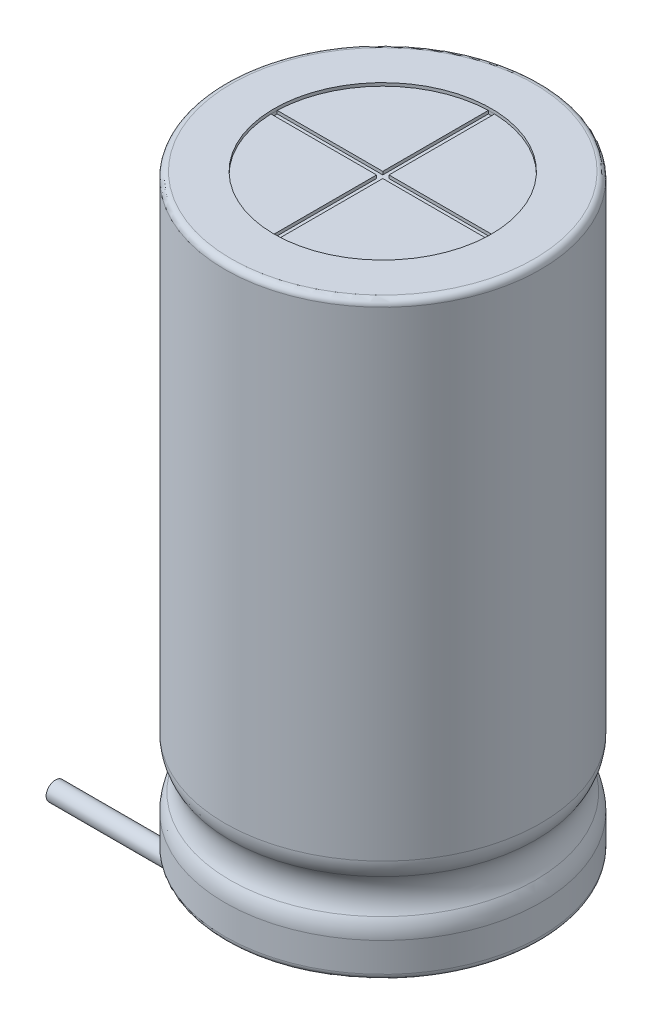
SolidWorks part; units mm, degrees
ref_plane "Płaszczyzna przednia" through (0, 0, 0) normal (0, 0, 1) x (1, 0, 0)
ref_plane "Płaszczyzna górna" through (0, 0, 0) normal (0, 1, 0) x (1, 0, 0)
ref_plane "Płaszczyzna prawa" through (0, 0, 0) normal (1, 0, 0) x (0, 0, -1)
sketch "Szkic1" plane through (0, 0, 0) normal (1, 0, 0) x (0, 0, -1)
  line L0 (0, 0) -> (4.88, 0)
  line L1 (5.08, 0.2) -> (5.08, 1.1437)
  line L2 (4.88, 19) -> (0, 19)
  line L3 (0, 19) -> (0, 0)
  line L4 (5.08, 3.3563) -> (5.08, 18.8)
  arc A0 (4.9162, 1.6927) -> (4.9162, 2.8073) centre (5.7673, 2.25) cw
  arc A1 (5.08, 18.8) -> (4.88, 19) centre (4.88, 18.8) ccw
  arc A2 (4.88, 0) -> (5.08, 0.2) centre (4.88, 0.2) ccw
  arc A3 (4.9162, 2.8073) -> (5.08, 3.3563) centre (4.0778, 3.3563) ccw
  arc A4 (4.9162, 1.6927) -> (5.08, 1.1437) centre (4.0778, 1.1437) cw
  point P8 (5.08, 19)
  point P11 (5.08, 0)
  point P17 (5.08, 3)
  dimension "D5" = 0.2
  dimension "D6" = 1.0022
  dimension "D3" = 1.0173
  dimension "D1" = 5.08
  dimension "D2" = 19
  dimension "D4" = 4.9162
  dimension "D7" = 1.1437
revolve "Obrót1" add sketch "Szkic1" angle 360 about L3
sketch "Szkic2" plane through (0, 19, 0) normal (0, 1, 0) x (1, 0, 0)
  circle A0 centre (0, 0) radius 3.5
  dimension "D1" = 7
extrude "Wytnij-wyciągnięcie1" cut sketch "Szkic2" against normal blind 0.1
sketch "Szkic3" plane through (0, 18.9, 0) normal (0, 1, 0) x (1, 0, 0)
  line L0 (0, 0) -> (0, 3.5) construction
  line L1 (0.1, 0) -> (0.1, 3.5)
  line L2 (-0.1, 0) -> (-0.1, 3.5)
  line L3 (0.1, 0) -> (-0.1, 0)
  line L4 (0.1, 3.5) -> (-0.1, 3.5)
  circle A0 centre (0, 0) radius 3.5 construction
  dimension "D1" = 0.1
  dimension "D2" = 0.1
extrude "Wytnij-wyciągnięcie2" cut sketch "Szkic3" against normal blind 0.1
pattern_circular "Szyk kołowy1" count 4 over 360 of "Wytnij-wyciągnięcie2"
sketch "Szkic4" plane through (0, 0, 0) normal (0, -1, 0) x (1, 0, 0)
  circle A0 centre (0, 0) radius 3.5
  dimension "D1" = 7
extrude "Wytnij-wyciągnięcie3" cut sketch "Szkic4" against normal blind 0.6
sketch "Szkic7" plane through (0, 0.6, 0) normal (0, -1, 0) x (-1, 0, 0)
  line L0 (0, 0) -> (0, -2.54) construction
  line L1 (0, 0) -> (0, 2.54) construction
  circle A0 centre (0, -2.54) radius 0.3
  circle A1 centre (0, 2.54) radius 0.3
  dimension "D3" = 0.6
  dimension "D4" = 0.6
  dimension "D1" = 2.54
  dimension "D2" = 2.54
extrude "Dodanie-wyciągnięcie1" [suppressed] add sketch "Szkic7" along normal blind 3.5
sketch "Эскиз1" plane through (0, 0, 0) normal (0, 0, 1) x (1, 0, 0)
  line L0 (0, 0.6) -> (0, 0)
  line L1 (0, -2.674) -> (0, 5.9479) construction
  line L2 (-1, -1) -> (-8, -1)
  arc A0 (-1, -1) -> (0, 0) centre (-1, 0) ccw
  point P8 (0, -1)
  dimension "D1" = 1
  dimension "D2" = 1
  dimension "D3" = 8
sweep "По траектории1" add profiles "Szkic7<2>" path "Эскиз1"
sketch "Szkic7<2>" plane through (0, 0.6, 0) normal (0, -1, 0) x (-1, 0, 0) same geometry as "Szkic7"
